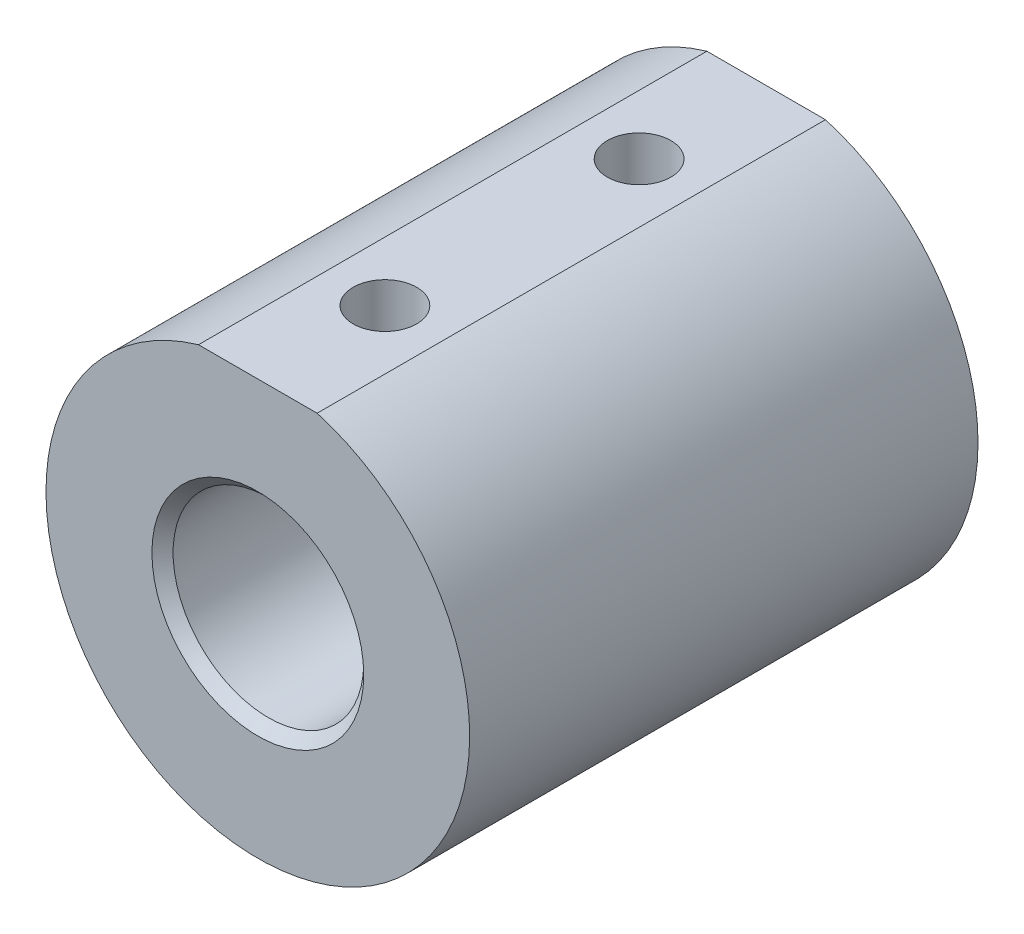
SolidWorks part; units mm, degrees
material "PE High Density"
ref_plane "Front Plane" through (0, 0, 0) normal (0, 0, 1) x (1, 0, 0)
ref_plane "Top Plane" through (0, 0, 0) normal (0, 1, 0) x (1, 0, 0)
ref_plane "Right Plane" through (0, 0, 0) normal (1, 0, 0) x (0, 0, -1)
sketch "Sketch1" plane through (0, 0, 0) normal (0, 0, 1) x (1, 0, 0)
  line L0 (0, 12.7) -> (0, 30.48) construction
  line L1 (-8.89, 30.48) -> (8.89, 30.48)
  circle A0 centre (0, 0) radius 14.2875
  circle A1 centre (0, 0) radius 31.75
  circle A2 centre (0, 0) radius 12.7 construction
  point P15 (0, 30.48)
  dimension "D1" = 28.575
  dimension "D2" = 25.4
  dimension "D5" = 63.5
  dimension "D4" = 17.78
extrude "Boss-Extrude1" add sketch "Sketch1" along normal blind 76.2 contours L1 A1 A0 region at (0, 29.5909, 0)
sketch "Sketch2" plane through (0, 30.48, 0) normal (0, 1, 0) x (1, 0, 0)
  line L0 (-8.89, -76.2) -> (-8.89, 0) construction
  line L3 (-8.89, -38.1) -> (8.89, -38.1) construction
  line L4 (8.89, -76.2) -> (8.89, 0) construction
  line L5 (0, -57.15) -> (0, -19.05) construction
  circle A0 centre (0, -57.15) radius 4.7625
  circle A1 centre (0, -19.05) radius 4.7625
  point P0 (0, -38.1)
  point P12 (0, -38.1)
  dimension "D1" = 9.525
  dimension "D2" = 9.525
  dimension "D3" = 38.1
extrude "Cut-Extrude1" cut sketch "Sketch2" against normal up to next
chamfer "Chamfer1" distance 1.5875 angle 45 2 edges at (14.2875, 0, 0) (14.2875, 0, 76.2)
